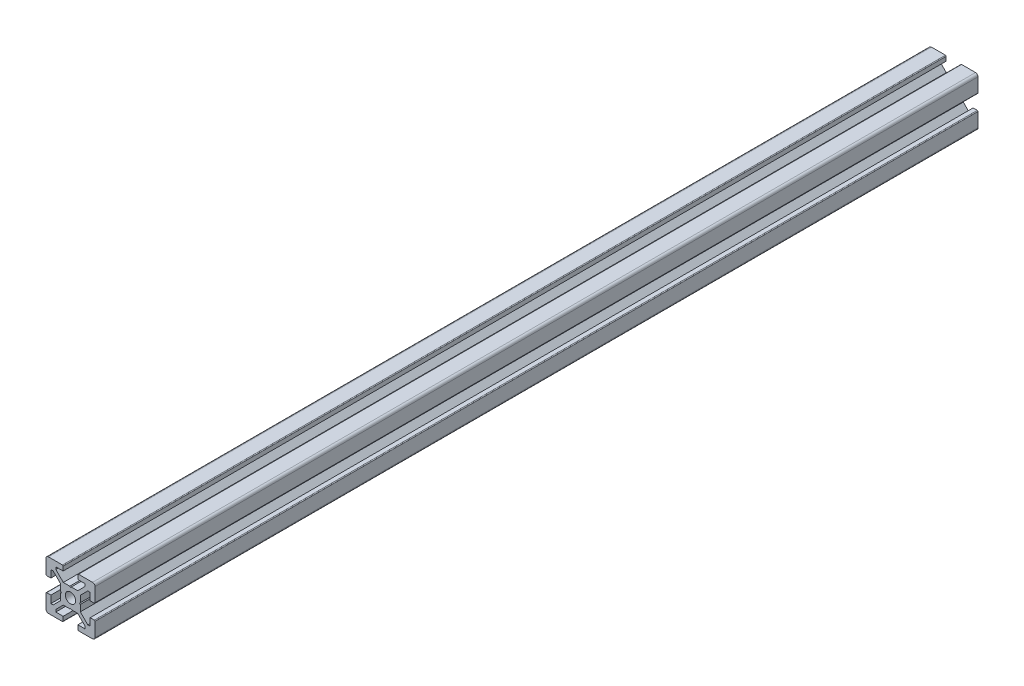
SolidWorks part; units mm, degrees
ref_plane "Front Plane" through (0, 0, 0) normal (0, 0, 1) x (1, 0, 0)
ref_plane "Top Plane" through (0, 0, 0) normal (0, 1, 0) x (1, 0, 0)
ref_plane "Right Plane" through (0, 0, 0) normal (1, 0, 0) x (0, 0, -1)
sketch "Sketch1" plane through (0, 0, 0) normal (0, 0, -1) x (-1, 0, 0)
  line L0 (10, 3.3) -> (10, 9)
  line L1 (9, 10) -> (3.3, 10)
  line L2 (3, 9.7) -> (3, 8)
  line L3 (3, 8) -> (6, 8)
  line L4 (6, 8) -> (6, 7.0607)
  line L5 (6, 7.0607) -> (2.9393, 4)
  line L6 (2.9393, 4) -> (0.3, 4)
  line L7 (0.3, 4) -> (0, 3.7)
  line L8 (0, 3.7) -> (-0.3, 4)
  line L9 (-0.3, 4) -> (-2.9393, 4)
  line L10 (-2.9393, 4) -> (-6, 7.0607)
  line L11 (-6, 7.0607) -> (-6, 8)
  line L12 (-6, 8) -> (-3, 8)
  line L13 (-3, 8) -> (-3, 9.7)
  line L14 (-3.3, 10) -> (-9, 10)
  line L15 (-10, 9) -> (-10, 3.3)
  line L16 (-9.7, 3) -> (-8, 3)
  line L17 (-8, 3) -> (-8, 6)
  line L18 (-8, 6) -> (-7.0607, 6)
  line L19 (-7.0607, 6) -> (-4, 2.9393)
  line L20 (-4, 2.9393) -> (-4, 0.3)
  line L21 (-4, 0.3) -> (-3.7, 0)
  line L22 (-3.7, 0) -> (-4, -0.3)
  line L23 (-4, -0.3) -> (-4, -2.9393)
  line L24 (-4, -2.9393) -> (-7.0607, -6)
  line L25 (-7.0607, -6) -> (-8, -6)
  line L26 (-8, -6) -> (-8, -3)
  line L27 (-8, -3) -> (-9.7, -3)
  line L28 (-10, -3.3) -> (-10, -9)
  line L29 (-9, -10) -> (-3.3, -10)
  line L30 (-3, -9.7) -> (-3, -8)
  line L31 (-3, -8) -> (-6, -8)
  line L32 (-6, -8) -> (-6, -7.0607)
  line L33 (-6, -7.0607) -> (-2.9393, -4)
  line L34 (-2.9393, -4) -> (-0.3, -4)
  line L35 (-0.3, -4) -> (0, -3.7)
  line L36 (0, -3.7) -> (0.3, -4)
  line L37 (0.3, -4) -> (2.9393, -4)
  line L38 (2.9393, -4) -> (6, -7.0607)
  line L39 (6, -7.0607) -> (6, -8)
  line L40 (6, -8) -> (3, -8)
  line L41 (3, -8) -> (3, -9.7)
  line L42 (3.3, -10) -> (9, -10)
  line L43 (10, -9) -> (10, -3.3)
  line L44 (9.7, -3) -> (8, -3)
  line L45 (8, -3) -> (8, -6)
  line L46 (8, -6) -> (7.0607, -6)
  line L47 (7.0607, -6) -> (4, -2.9393)
  line L48 (4, -2.9393) -> (4, -0.3)
  line L49 (4, -0.3) -> (3.7, 0)
  line L50 (3.7, 0) -> (4, 0.3)
  line L51 (4, 0.3) -> (4, 2.9393)
  line L52 (4, 2.9393) -> (7.0607, 6)
  line L53 (7.0607, 6) -> (8, 6)
  line L54 (8, 6) -> (8, 3)
  line L55 (8, 3) -> (9.7, 3)
  line L56 (9, -9) -> (-9, 9) construction
  line L57 (-9, -9) -> (9, 9) construction
  line L58 (-3.7, 0) -> (3.7, 0) construction
  line L59 (0, -3.7) -> (0, 3.7) construction
  circle A0 centre (0, 0) radius 2.1
  arc A1 (10, 9) -> (9, 10) centre (9, 9) ccw
  arc A2 (3.3, 10) -> (3, 9.7) centre (3.3, 9.7) ccw
  arc A3 (-3, 9.7) -> (-3.3, 10) centre (-3.3, 9.7) ccw
  arc A4 (-9, 10) -> (-10, 9) centre (-9, 9) ccw
  arc A5 (-10, 3.3) -> (-9.7, 3) centre (-9.7, 3.3) ccw
  arc A6 (-9.7, -3) -> (-10, -3.3) centre (-9.7, -3.3) ccw
  arc A7 (-10, -9) -> (-9, -10) centre (-9, -9) ccw
  arc A8 (-3.3, -10) -> (-3, -9.7) centre (-3.3, -9.7) ccw
  arc A9 (3, -9.7) -> (3.3, -10) centre (3.3, -9.7) ccw
  arc A10 (9, -10) -> (10, -9) centre (9, -9) ccw
  arc A11 (10, -3.3) -> (9.7, -3) centre (9.7, -3.3) ccw
  arc A12 (9.7, 3) -> (10, 3.3) centre (9.7, 3.3) ccw
  point P83 (0, 0)
  point P85 (0, 0)
  point P86 (0, 0)
  dimension "D1" = 1
  dimension "D4" = 0.3
  dimension "D10" = 4.2
  dimension "D2" = 20
  dimension "D3" = 6
  dimension "D5" = 3
  dimension "D6" = 1.7
  dimension "D7" = 0.9393
  dimension "D8" = 0.6
  dimension "D9" = 4
  dimension "D11" = 3.0607
  dimension "D12" = 3.0607
  dimension "D13" = 3.0607
  dimension "D14" = 5.7
  dimension "D15" = 5.7
  dimension "D16" = 0.9393
  dimension "D17" = 0.9393
  dimension "D18" = 3.0607
extrude "Boss-Extrude1" add sketch "Sketch1" against normal mid plane 360.4
ref_axis "Axis1" through (0, 0, 180.2) along (0, 0, -1)
